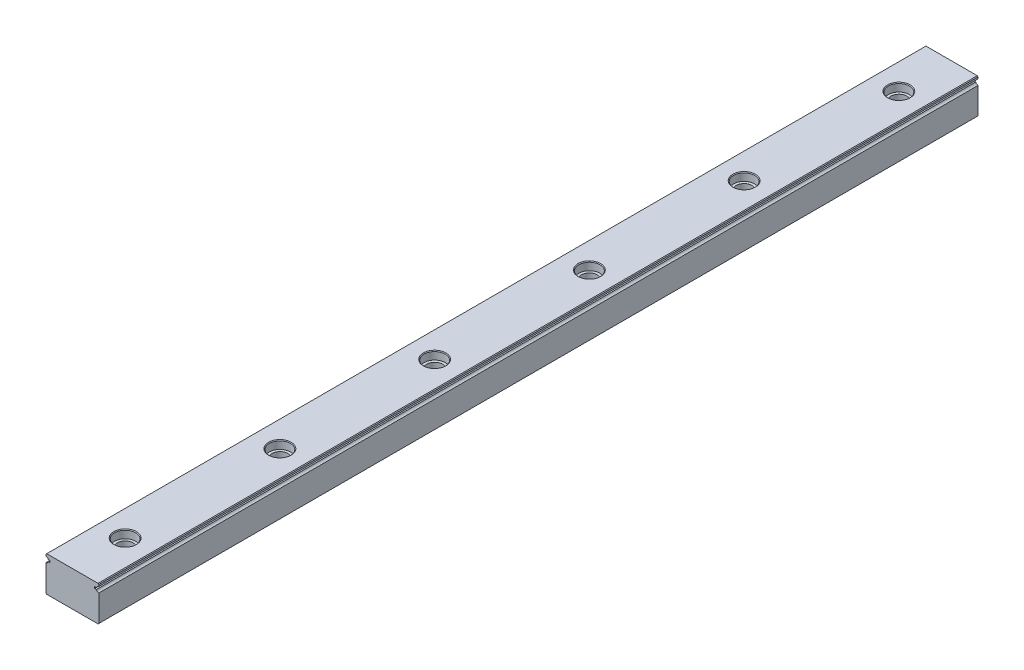
SolidWorks part; units mm, degrees
ref_plane "Спереди" through (0, 0, 0) normal (0, 0, 1) x (1, 0, 0)
ref_plane "Сверху" through (0, 0, 0) normal (0, 1, 0) x (1, 0, 0)
ref_plane "Справа" through (0, 0, 0) normal (1, 0, 0) x (0, 0, -1)
sketch "Sketch1" plane through (0, 0, 0) normal (0, 0, 1) x (1, 0, 0)
  line L0 (0, 0) -> (0, 4.3706) construction
  line L1 (-7.3, -5) -> (7.3, -5)
  line L2 (-7.5, -4.8) -> (-7.5, 2.7063)
  line L3 (-7.3, 5) -> (7.3, 5)
  line L4 (7.5, -4.8) -> (7.5, 2.7063)
  line L5 (-7.5, -5) -> (7.5, 5) construction
  line L6 (-7.5, 5) -> (7.5, -5) construction
  line L7 (-7.5, 4.2937) -> (-7.5, 4.8)
  line L8 (7.5, 4.2937) -> (7.5, 4.8)
  line L9 (-7.5, -4.8) -> (-7.3, -5)
  line L10 (7.3, -5) -> (7.5, -4.8)
  line L11 (7.3, 5) -> (7.5, 4.8)
  line L12 (-7.5, 4.8) -> (-7.3, 5)
  line L13 (6.8401, 3.25) -> (6.3401, 3.25)
  line L14 (-6.8401, 3.25) -> (-6.3401, 3.25)
  line L15 (6.3401, 3.25) -> (6.3401, 3.75)
  line L16 (-6.8401, 3.75) -> (-6.3401, 3.75)
  line L17 (-6.3401, 3.25) -> (-6.3401, 3.75)
  line L18 (6.8401, 3.75) -> (6.3401, 3.75)
  arc A0 (-7.5, 4.2937) -> (-6.8401, 3.75) centre (-7.6, 3.5) cw
  arc A1 (7.5, 4.2937) -> (6.8401, 3.75) centre (7.6, 3.5) ccw
  arc A2 (-6.8401, 3.25) -> (-7.5, 2.7063) centre (-7.6, 3.5) cw
  arc A3 (6.8401, 3.25) -> (7.5, 2.7063) centre (7.6, 3.5) ccw
  point P0 (0, 0)
  dimension "D4" = 0.8
  dimension "D5" = 0.1
  dimension "D1" = 15
  dimension "D2" = 10
  dimension "D3" = 1.5
  dimension "D6" = 0.5
  dimension "D7" = 0.5
extrude "Extrude1" add sketch "Sketch1" along normal blind 250
sketch "Sketch2" plane through (0, 5, 0) normal (0, 1, 0) x (1, 0, 0)
  line L0 (0, 0) -> (0, -15) construction
  circle A0 centre (0, -15) radius 2.25
  circle A1 centre (0, -15) radius 3
  dimension "D1" = 4.5
  dimension "D2" = 6
  dimension "D3" = 15
extrude "Extrude2" cut sketch "Sketch2" against normal up to next contours A0 region at (0, 5, 15)
extrude "Extrude4" cut sketch "Sketch" against normal blind 2.3
sketch "Sketch" plane through (0, 5, 0) normal (0, 1, 0) x (1, 0, 0) same geometry as "Sketch2"
chamfer "Chamfer1" distance 0.2 angle 45 2 edges at (0, -5, 17.25) (0, 5, 18)
pattern_linear "LPattern1" count 6 spacing 44 along (0, 0, 1) of "Extrude4", "Chamfer1", "Extrude2"
